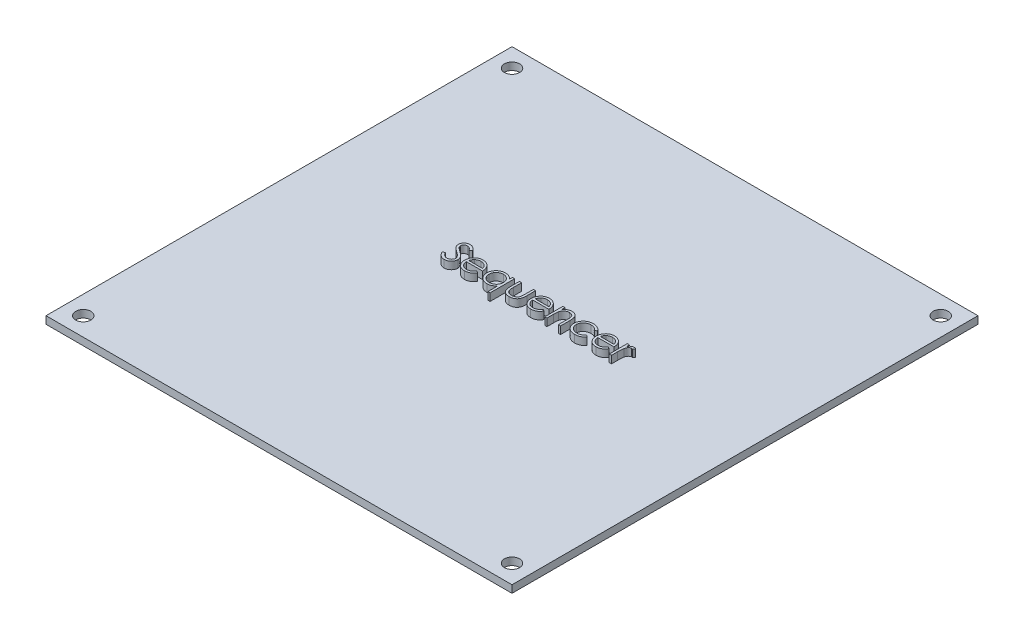
SolidWorks part; units mm, degrees
ref_plane "Front Plane" through (0, 0, 0) normal (0, 0, 1) x (1, 0, 0)
ref_plane "Top Plane" through (0, 0, 0) normal (0, 1, 0) x (1, 0, 0)
ref_plane "Right Plane" through (0, 0, 0) normal (1, 0, 0) x (0, 0, -1)
sketch "Sketch18" plane through (0, 0, 0) normal (0, 1, 0) x (1, 0, 0)
  line L1 (50, -50) -> (-50, -50)
  line L2 (50, -50) -> (50, 50)
  line L3 (50, 50) -> (-50, 50)
  line L4 (-50, -50) -> (-50, 50)
  line L5 (50, -50) -> (-50, 50) construction
  line L6 (50, 50) -> (-50, -50) construction
  point P0 (0, 0)
  dimension "D1" = 100
  dimension "D2" = 100
extrude "Boss-Extrude6" add sketch "Sketch18" along normal blind 1.6
hole_wizard "#4 Clearance Hole3" positions "Sketch23" profile "Sketch22" hole size "#4" standard "ANSI Inch" end condition through all
sketch "Sketch23" plane through (0, 1.6, 0) normal (0, 1, 0) x (1, 0, 0)
  line L0 (50, 50) -> (-50, 50) construction
  line L1 (-50, 50) -> (-50, -50) construction
  line L2 (50, -50) -> (50, 50) construction
  line L3 (-50, -50) -> (50, -50) construction
  point P0 (-46, 46)
  point P2 (46, 46)
  point P4 (46, -46)
  point P6 (-46, -46)
  point P19 (45.6335, 50)
  point P20 (0, 0)
  dimension "D1" = 4
  dimension "D2" = 4
  dimension "D3" = 4
  dimension "D4" = 4
  dimension "D5" = 4
  dimension "D6" = 4
  dimension "D7" = 4
  dimension "D8" = 4
sketch "Sketch22" plane through (-46, 1.6, -46) normal (1, 0, 0) x (0, 0, 1)
  line L0 (0, 0) -> (0, 1.6)
  line L1 (0, 1.6) -> (1.6319, 1.6)
  line L2 (1.6319, 1.6) -> (1.6319, 0)
  line L5 (1.6319, 0) -> (0, 0)
  line L11 (0, -6.35) -> (0, 107.95) construction
  dimension "Thru Hole Dia." = 3.2639
  dimension "Thru Hole Depth" = 1.6
sketch "Sketch25" plane through (0, 1.6, 0) normal (0, 1, 0) x (1, 0, 0)
  text T0 "Sequencer" font "Century Gothic" height in points 20
extrude "Boss-Extrude8" add sketch "Sketch25" along normal blind 1.6
